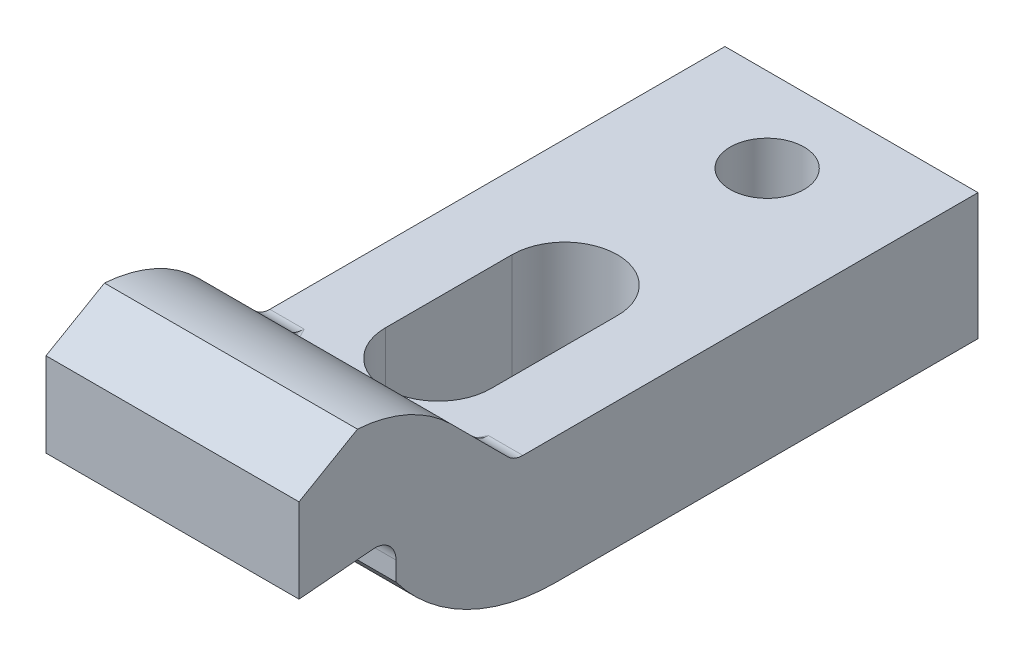
SolidWorks part; units mm, degrees
material "1.0553 (S355J0)"
ref_plane "Front Plane" through (0, 0, 0) normal (0, 0, 1) x (1, 0, 0)
ref_plane "Top Plane" through (0, 0, 0) normal (0, 1, 0) x (1, 0, 0)
ref_plane "Right Plane" through (0, 0, 0) normal (1, 0, 0) x (0, 0, -1)
sketch "Sketch1" plane through (0, 0, 0) normal (1, 0, 0) x (0, 0, -1)
  line L0 (0, 0) -> (0, 20)
  line L1 (0, 20) -> (13.8564, 28)
  line L2 (53.0711, 3) -> (161, 3)
  line L3 (161, 3) -> (161, -27)
  line L4 (161, -27) -> (61, -27)
  line L5 (17.5669, 1.5276) -> (0, 0)
  line L6 (23, -3.4537) -> (23, -8)
  line L7 (49.5355, 4.4645) -> (36.1662, 17.8338)
  arc A2 (23, -8) -> (61, -27) centre (61, 20.5) ccw
  arc A3 (13.8564, 28) -> (36.1662, 17.8338) centre (11.4174, -6.9149) cw
  arc A4 (23, -3.4537) -> (17.5669, 1.5276) centre (18, -3.4537) ccw
  arc A5 (49.5355, 4.4645) -> (53.0711, 3) centre (53.0711, 8) ccw
  point P20 (23, 2)
  point P23 (51, 3)
  dimension "D1" = 161
  dimension "D6" = 23
  dimension "D7" = 45
  dimension "D10" = 35
  dimension "D14" = 5
  dimension "D15" = 5
  dimension "D2" = 20
  dimension "D3" = 55
  dimension "D4" = 60
  dimension "D5" = 110
  dimension "D8" = 30
  dimension "D9" = 28
  dimension "D11" = 100
  dimension "D12" = 10
  dimension "D13" = 8
extrude "Boss-Extrude1" add sketch "Sketch1" along normal mid plane 60
sketch "Sketch2" plane through (0, 3, 0) normal (0, 1, 0) x (1, 0, 0)
  line L0 (30, 0) -> (-30, 0) construction
  line L1 (0, 161) -> (0, 138.8507) construction
  circle A0 centre (0, 63) radius 25
  point P4 (0, 38)
  dimension "D1" = 50
  dimension "D2" = 63
  dimension "D3" = 38
extrude "Cut-Extrude1" cut sketch "Sketch2" along normal up to next
fillet "Fillet1" radius 1 1 edges at (0, 3, -38)
hole_wizard "M20 Tapped Hole1" positions "Sketch4" profile "Sketch5" tap size "M20" standard "ISO" end condition up to next
sketch "Sketch4" plane through (0, 3, 0) normal (0, 1, 0) x (1, 0, 0)
  line L0 (0, 0) -> (0, 93.9225) construction
  line L2 (30, 161) -> (-30, 161) construction
  point P0 (0, 141)
  dimension "D1" = 20
sketch "Sketch5" plane through (0, 3, -141) normal (1, 0, 0) x (0, 0, 1)
  line L0 (0, 0) -> (0, 30)
  line L1 (0, 30) -> (8.75, 30)
  line L2 (8.75, 30) -> (8.75, 0)
  line L5 (8.75, 0) -> (0, 0)
  line L11 (0, -6.35) -> (0, 107.95) construction
  dimension "Thru Tap Drill Dia." = 17.5
  dimension "Thru Tap Drill Depth" = 30
cosmetic thread "Hole Thread1" parameters "D2"=20
sketch "Sketch8" plane through (0, 3, 0) normal (0, 1, 0) x (1, 0, 0)
  line L0 (0, 63) -> (0, 93) construction
  line L1 (-12.5, 63) -> (-12.5, 93)
  line L2 (12.5, 63) -> (12.5, 93)
  line L3 (30, 0) -> (-30, 0) construction
  arc A0 (-12.5, 63) -> (12.5, 63) centre (0, 63) ccw
  arc A1 (12.5, 93) -> (-12.5, 93) centre (0, 93) ccw
  point P3 (0, 78)
  point P10 (0, 50.5)
  point P11 (0, 105.5)
  dimension "D3" = 12.5
  dimension "D1" = 63
  dimension "D2" = 30
  dimension "D4" = 55
  dimension "D5" = 25
extrude "Cut-Extrude2" cut sketch "Sketch8" against normal up to next
equation "\"D2@Sketch2\"=38+\"D1@Sketch2\"/2"
